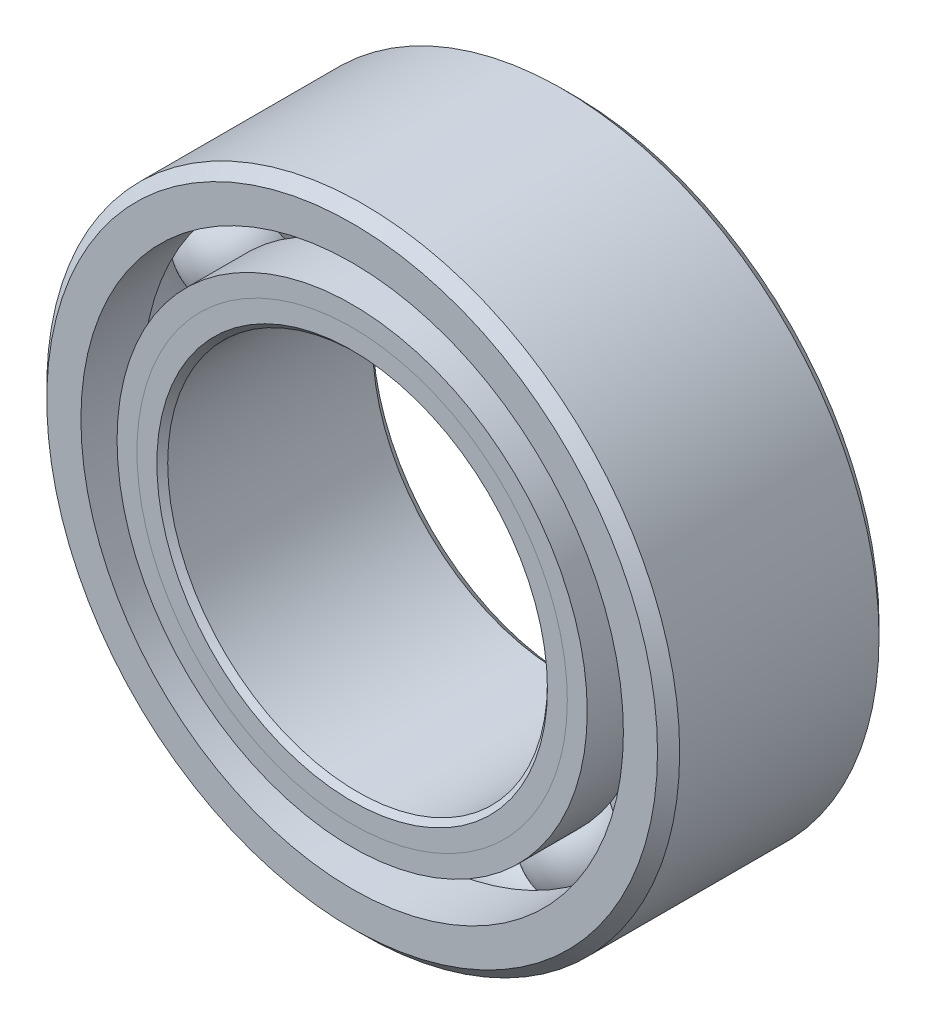
SolidWorks part; units mm, degrees
material "Alloy Steel"
ref_plane "Front Plane" through (0, 0, 0) normal (0, 0, 1) x (1, 0, 0)
ref_plane "Top Plane" through (0, 0, 0) normal (0, 1, 0) x (1, 0, 0)
ref_plane "Right Plane" through (0, 0, 0) normal (1, 0, 0) x (0, 0, -1)
sketch "Sketch1" plane through (0, 0, 0) normal (1, 0, 0) x (0, 0, -1)
  line L0 (-1.3891, 0) -> (1.3891, 0) construction
  line L1 (0, 3.9688) -> (0, -3.9688) construction
  line L2 (1.2502, 3.9688) -> (-1.2502, 3.9688)
  line L3 (-1.2502, 3.9688) -> (-1.3891, 3.8298)
  line L4 (-1.3891, 3.8298) -> (-1.3891, 3.4018)
  line L5 (-1.3891, 3.4018) -> (-0.6174, 3.4018)
  line L6 (1.3891, 3.4018) -> (0.6174, 3.4018)
  line L7 (1.3891, 3.8298) -> (1.3891, 3.4018)
  line L8 (1.2502, 3.9688) -> (1.3891, 3.8298)
  line L9 (0, 3.9688) -> (0, 3.175) construction
  line L10 (0, 3.175) -> (0, 2.3813) construction
  arc A0 (-0.6174, 3.4018) -> (0.6174, 3.4018) centre (0, 3.175) cw
  point P14 (0, 2.3813)
  dimension "Width" = 2.7781
  dimension "OD" = 7.9375
  dimension "D1" = 45
  dimension "D2" = 0.1389
  dimension "D3" = 1.2347
  dimension "D4" = 0.2268
revolve "Revolve1" add sketch "Sketch1" angle 360 about L0
sketch "Sketch2" plane through (0, 0, 0) normal (1, 0, 0) x (0, 0, -1)
  line L0 (-1.3891, 2.9482) -> (-0.6174, 2.9482)
  line L1 (-1.3891, 3.8298) -> (-1.3891, -3.8298) construction
  line L2 (-1.3891, 2.9482) -> (-1.3891, 2.6987)
  line L3 (-1.3891, 2.6987) -> (-1.1396, 2.4493)
  line L4 (-1.1396, 2.4493) -> (0, 2.4493)
  line L5 (0, 3.9688) -> (0, -3.9688) construction
  line L6 (0, 2.4493) -> (0, 2.5173)
  line L7 (0, 2.5173) -> (0, 2.3813) construction
  line L8 (-1.3891, 2.9482) -> (-1.3891, 2.4493) construction
  line L9 (-1.3891, 2.4493) -> (-1.1396, 2.4493) construction
  arc A0 (-0.6174, 2.9482) -> (0, 2.5173) centre (0, 3.175) ccw
  arc A1 (0.6174, 3.4018) -> (-0.6174, 3.4018) centre (0, 3.175) ccw construction
  circle A2 centre (0, 3.175) radius 0.6577 construction
  dimension "D1" = 45
revolve "Revolve2" add sketch "Sketch2" angle 360 about L0
sketch "Sketch3" plane through (0, 0, 0) normal (1, 0, 0) x (0, 0, -1)
  line L0 (-1.3891, 2.6987) -> (-1.1396, 2.4493)
  line L1 (-1.1396, 2.4493) -> (0, 2.4493)
  line L2 (0, 2.4493) -> (0, 2.5173)
  line L3 (-1.3891, 2.6987) -> (-1.3891, 2.4493)
  line L4 (-1.3891, 2.9482) -> (-1.3891, 2.4493) construction
  line L5 (-1.3891, 2.4493) -> (-1.321, 2.3812)
  line L6 (-1.321, 2.3812) -> (1.2502, 2.3813)
  line L7 (1.2502, 3.9688) -> (1.2502, -3.9688) construction
  line L8 (1.2502, 2.3813) -> (1.3891, 2.5202)
  line L9 (1.3891, -3.8298) -> (1.3891, 3.8298) construction
  line L10 (1.3891, 2.5202) -> (1.3891, 2.9482)
  line L11 (1.3891, 2.9482) -> (0.6174, 2.9482)
  line L13 (1.2502, 3.9688) -> (1.3891, 3.8298) construction
  circle A0 centre (0, 3.175) radius 0.6577 construction
  arc A1 (0.6174, 2.9482) -> (0, 2.5173) centre (0, 3.175) cw
revolve "Revolve3" add sketch "Sketch3" angle 360 about L0
sketch "Sketch4" plane through (0, 0, 0) normal (1, 0, 0) x (0, 0, -1)
  line L0 (-0.6577, 3.175) -> (0.6577, 3.175)
  circle A1 centre (0, 3.175) radius 0.6577 construction
  arc A2 (-0.6577, 3.175) -> (0.6577, 3.175) centre (0, 3.175) cw
  arc A3 (0.6174, 3.4018) -> (-0.6174, 3.4018) centre (0, 3.175) ccw construction
revolve "Revolve4" add sketch "Sketch4" angle 360 about L0
ref_axis "Axis1" through (0, 0, -1.3891) along (0, 0, 1)
pattern_circular "CirPattern1" count 12 every 30 about axis through (0, 0, -1.3891) along (0, 0, 1) of bodies 104
equation "\"D2@Sketch1\" = \"Width@Sketch1\"*.05"
equation "\"D3@Sketch1\" = \"Width@Sketch1\"/2.25"
equation "\"D4@Sketch1\" = (((\"OD@Sketch1\"-\"Width@Sketch1\")/2)/3.25)/3.5"
equation "\"D2@CirPattern1\" = 360/\"Balls@CirPattern1\""
